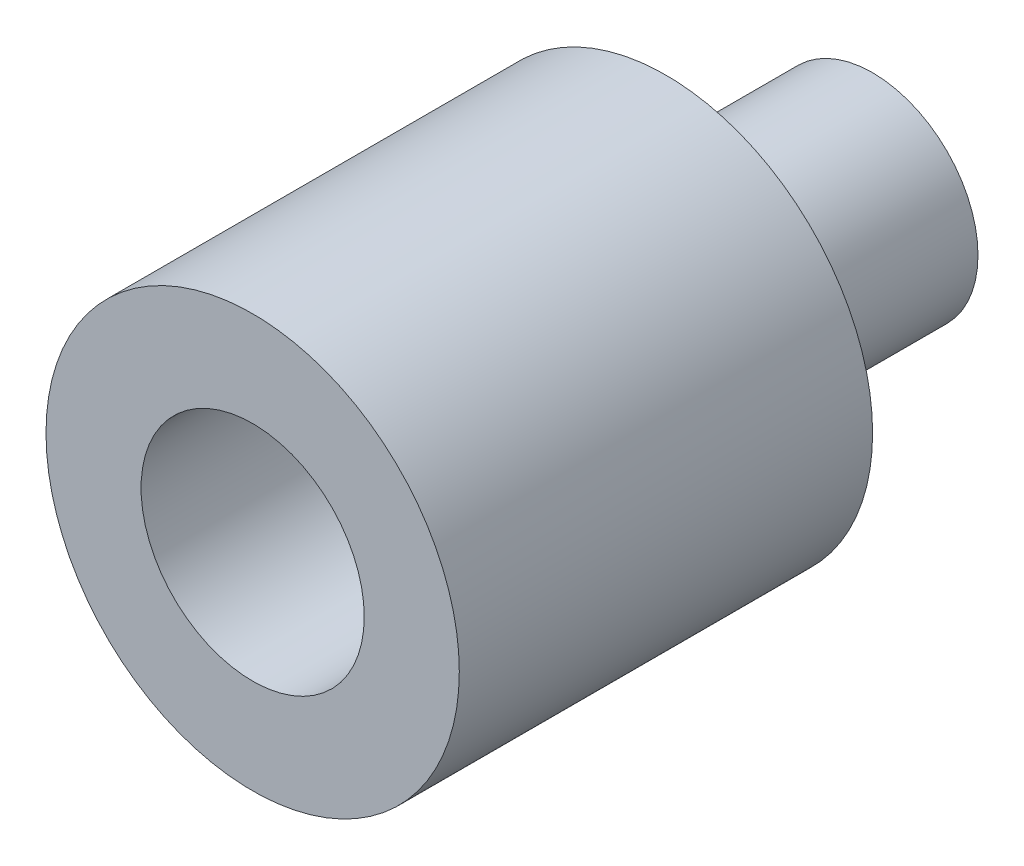
SolidWorks part; units mm, degrees
material "ABS"
ref_plane "X-Y Datum" through (0, 0, 0) normal (0, 0, 1) x (1, 0, 0)
ref_plane "X-Z Datum" through (0, 0, 0) normal (0, 1, 0) x (1, 0, 0)
ref_plane "Y-Z Datum" through (0, 0, 0) normal (1, 0, 0) x (0, 0, -1)
sketch "Sketch1" plane through (0, 0, 0) normal (0, 0, 1) x (1, 0, 0)
  circle A0 centre (0, 0) radius 2.55
  dimension "D1" = 5.1
extrude "Boss-Extrude1" add sketch "Sketch1" along normal blind 5
sketch "Sketch2" plane through (0, 0, 5) normal (0, 0, 1) x (1, 0, 0)
  circle A0 centre (0, 0) radius 5
  circle A1 centre (0, 0) radius 2.7 construction
  dimension "D1" = 5.4
  dimension "D2" = 10
extrude "Boss-Extrude2" add sketch "Sketch2" along normal blind 10 contours A0
sketch "Sketch3" plane through (0, 0, 15) normal (0, 0, 1) x (1, 0, 0)
  circle A0 centre (0, 0) radius 2.7
  dimension "D1" = 5.4
extrude "Cut-Extrude1" cut sketch "Sketch3" against normal blind 8
